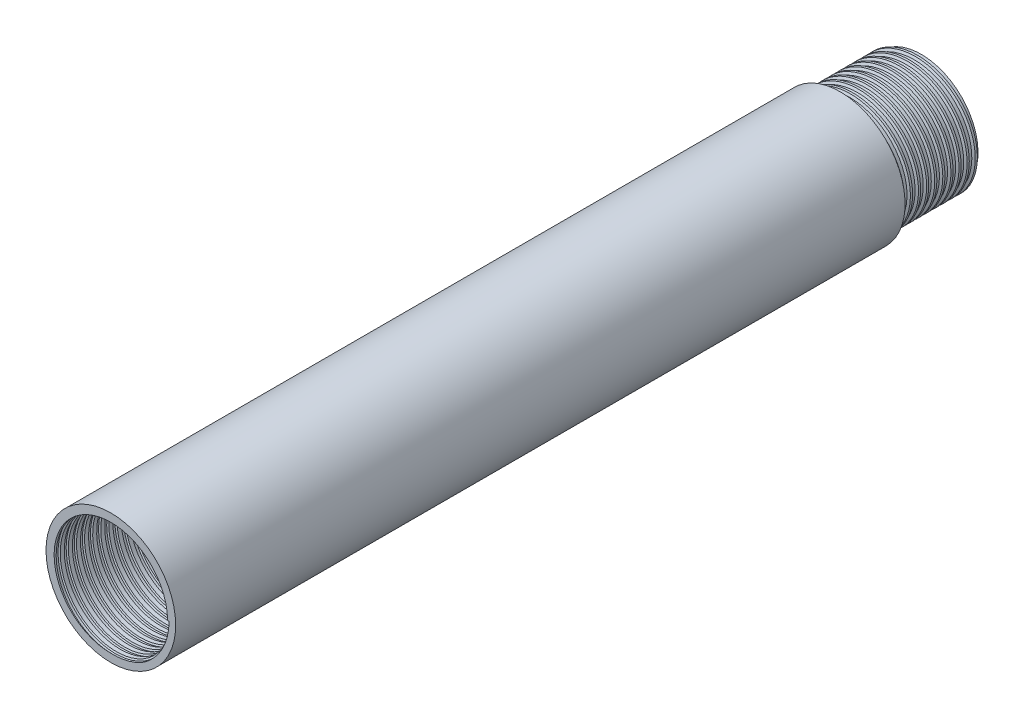
SolidWorks part; units mm, degrees
ref_plane "Front Plane" through (0, 0, 0) normal (0, 0, 1) x (1, 0, 0)
ref_plane "Top Plane" through (0, 0, 0) normal (0, 1, 0) x (1, 0, 0)
ref_plane "Right Plane" through (0, 0, 0) normal (1, 0, 0) x (0, 0, -1)
sketch "Sketch1" plane through (0, 0, 0) normal (0, 0, 1) x (1, 0, 0)
  circle A0 centre (0, 0) radius 9
  circle A1 centre (0, 0) radius 12
  dimension "D1" = 18
  dimension "D2" = 24
extrude "Boss-Extrude1" add sketch "Sketch1" along normal blind 150
sketch "Sketch2" plane through (0, 0, 0) normal (0, 0, -1) x (-1, 0, 0)
  circle A0 centre (0, 0) radius 12
  circle A1 centre (0, 0) radius 10.5
  dimension "D1" = 21
extrude "Cut-Extrude1" cut sketch "Sketch2" against normal blind 15
sketch "Sketch8" plane through (0, 0, 150) normal (0, 0, 1) x (1, 0, 0)
  circle A0 centre (0, 0) radius 9
  circle A1 centre (0, 0) radius 10.5
  dimension "D1" = 21
extrude "Cut-Extrude3" cut sketch "Sketch8" against normal blind 15
sketch "Sketch9" plane through (0, 0, 150) normal (0, 0, 1) x (1, 0, 0)
  circle A0 centre (0, 0) radius 10.25
curve "Helix/Spiral3" pitch 1.5 height 15 turns 10
sketch "Sketch10" plane through (0, 0, 0) normal (0, 1, 0) x (1, 0, 0)
  line L0 (10.2387, -148.4889) -> (10.7749, -148.4889) construction
  line L5 (10.2387, -147.9889) -> (10.2387, -148.9889)
  line L6 (10.2387, -148.9889) -> (10.7749, -148.7389)
  line L7 (10.7749, -148.7389) -> (10.7749, -148.2389)
  line L8 (10.2387, -147.9889) -> (10.7749, -148.2389)
  spline S1 degree 3 poles (10.25, -150) (10.25, -149.969) (9.7163, -149.9062) (7.4365, -149.8125) (4.0246, -149.7187) (0, -149.625) (-4.0246, -149.5312) (-7.4365, -149.4375) (-9.7163, -149.3437) (-10.5168, -149.25) (-9.7163, -149.1562) (-7.4365, -149.0625) (-2.8873, -148.9375) (2.8873, -148.8125) (7.4365, -148.6875) (9.7163, -148.5937) (10.5168, -148.5) (9.7163, -148.4062) (7.4365, -148.3125) (2.8873, -148.1875) (-2.8873, -148.0625) (-7.4365, -147.9375) (-9.7163, -147.8437) (-10.5168, -147.75) (-9.7163, -147.6562) (-7.4365, -147.5625) (-2.8873, -147.4375) (2.8873, -147.3125) (7.4365, -147.1875) (9.7163, -147.0938) (10.5168, -147) (9.7163, -146.9062) (7.4365, -146.8125) (2.8873, -146.6875) (-2.8873, -146.5625) (-7.4365, -146.4375) (-9.7163, -146.3438) (-10.5168, -146.25) (-9.7163, -146.1562) (-7.4365, -146.0625) (-2.8873, -145.9375) (2.8873, -145.8125) (7.4365, -145.6875) (9.7163, -145.5937) (10.5168, -145.5) (9.7163, -145.4062) (7.4365, -145.3125) (2.8873, -145.1875) (-2.8873, -145.0625) (-7.4365, -144.9375) (-9.7163, -144.8438) (-10.5168, -144.75) (-9.7163, -144.6562) (-7.4365, -144.5625) (-2.8873, -144.4375) (2.8873, -144.3125) (7.4365, -144.1875) (9.7163, -144.0937) (10.5168, -144) (9.7163, -143.9062) (7.4365, -143.8125) (2.8873, -143.6875) (-2.8873, -143.5625) (-7.4365, -143.4375) (-9.7163, -143.3437) (-10.5168, -143.25) (-9.7163, -143.1562) (-7.4365, -143.0625) (-2.8873, -142.9375) (2.8873, -142.8125) (7.4365, -142.6875) (9.7163, -142.5938) (10.5168, -142.5) (9.7163, -142.4062) (7.4365, -142.3125) (2.8873, -142.1875) (-2.8873, -142.0625) (-7.4365, -141.9375) (-9.7163, -141.8438) (-10.5168, -141.75) (-9.7163, -141.6562) (-7.4365, -141.5625) (-2.8873, -141.4375) (2.8873, -141.3125) (7.4365, -141.1875) (9.7163, -141.0938) (10.5168, -141) (9.7163, -140.9062) (7.4365, -140.8125) (2.8873, -140.6875) (-2.8873, -140.5625) (-7.4365, -140.4375) (-9.7163, -140.3437) (-10.5168, -140.25) (-9.7163, -140.1563) (-7.4365, -140.0625) (-2.8873, -139.9375) (2.8873, -139.8125) (7.4365, -139.6875) (9.7163, -139.5938) (10.5168, -139.5) (9.7163, -139.4062) (7.4365, -139.3125) (2.8873, -139.1875) (-2.8873, -139.0625) (-7.4365, -138.9375) (-9.7163, -138.8438) (-10.5168, -138.75) (-9.7163, -138.6562) (-7.4365, -138.5625) (-2.8873, -138.4375) (2.8873, -138.3125) (7.4365, -138.1875) (9.7163, -138.0937) (10.5168, -138) (9.7163, -137.9062) (7.4365, -137.8125) (2.8873, -137.6875) (-2.8873, -137.5625) (-7.4365, -137.4375) (-9.7163, -137.3437) (-10.5168, -137.25) (-9.7163, -137.1562) (-7.4365, -137.0625) (-2.8873, -136.9375) (2.8873, -136.8125) (7.4365, -136.6875) (9.7163, -136.5938) (10.5168, -136.5) (9.7163, -136.4063) (7.4365, -136.3125) (2.8873, -136.1875) (-2.8873, -136.0625) (-7.4365, -135.9375) (-9.7163, -135.8438) (-10.5168, -135.75) (-9.7163, -135.6563) (-7.4365, -135.5625) (-4.0246, -135.4688) (0, -135.375) (4.0246, -135.2813) (7.4365, -135.1875) (9.7163, -135.0938) (10.25, -135.031) (10.25, -135) knots 0 0 0 0 0.00625 0.0125 0.01875 0.025 0.03125 0.0375 0.04375 0.05 0.05625 0.0625 0.06875 0.08125 0.0875 0.09375 0.1 0.10625 0.1125 0.11875 0.13125 0.1375 0.14375 0.15 0.15625 0.1625 0.16875 0.18125 0.1875 0.19375 0.2 0.20625 0.2125 0.21875 0.23125 0.2375 0.24375 0.25 0.25625 0.2625 0.26875 0.28125 0.2875 0.29375 0.3 0.30625 0.3125 0.31875 0.33125 0.3375 0.34375 0.35 0.35625 0.3625 0.36875 0.38125 0.3875 0.39375 0.4 0.40625 0.4125 0.41875 0.43125 0.4375 0.44375 0.45 0.45625 0.4625 0.46875 0.48125 0.4875 0.49375 0.5 0.50625 0.5125 0.51875 0.53125 0.5375 0.54375 0.55 0.55625 0.5625 0.56875 0.58125 0.5875 0.59375 0.6 0.60625 0.6125 0.61875 0.63125 0.6375 0.64375 0.65 0.65625 0.6625 0.66875 0.68125 0.6875 0.69375 0.7 0.70625 0.7125 0.71875 0.73125 0.7375 0.74375 0.75 0.75625 0.7625 0.76875 0.78125 0.7875 0.79375 0.8 0.80625 0.8125 0.81875 0.83125 0.8375 0.84375 0.85 0.85625 0.8625 0.86875 0.88125 0.8875 0.89375 0.9 0.90625 0.9125 0.91875 0.93125 0.9375 0.94375 0.95 0.95625 0.9625 0.96875 0.975 0.98125 0.9875 0.99375 1 1 1 1 construction
  dimension "D1" = 0.5
  dimension "D2" = 0.25
  dimension "D3" = 65
sweep "Cut-Sweep1" cut profiles "Sketch10" path "Helix/Spiral3"
sketch "Sketch11" plane through (0, 0, 0) normal (0, 0, -1) x (-1, 0, 0)
  circle A0 centre (0, 0) radius 10.5
curve "Helix/Spiral4" pitch 1.5 height 15 turns 10
sketch "Sketch12" plane through (0, 0, 0) normal (0, 1, 0) x (1, 0, 0)
  line L0 (-10.5, -1.5) -> (-10.9289, -1.5) construction
  line L1 (-10.5, 0) -> (-10.5, -15) construction
  line L2 (-10.5, -1.9) -> (-10.5, -1.1)
  line L3 (-10.5, -1.1) -> (-10.9289, -1.3)
  line L4 (-10.9289, -1.3) -> (-10.9289, -1.7)
  line L5 (-10.5, -1.9) -> (-10.9289, -1.7)
  spline S0 degree 3 poles (-10.5, 0) (-10.5, -0.031) (-9.9533, -0.0938) (-7.6179, -0.1875) (-4.1228, -0.2813) (0, -0.375) (4.1228, -0.4688) (7.6179, -0.5625) (9.9533, -0.6563) (10.7734, -0.75) (9.9533, -0.8438) (7.6179, -0.9375) (2.9577, -1.0625) (-2.9577, -1.1875) (-7.6179, -1.3125) (-9.9533, -1.4063) (-10.7734, -1.5) (-9.9533, -1.5938) (-7.6179, -1.6875) (-2.9577, -1.8125) (2.9577, -1.9375) (7.6179, -2.0625) (9.9533, -2.1562) (10.7734, -2.25) (9.9533, -2.3438) (7.6179, -2.4375) (2.9577, -2.5625) (-2.9577, -2.6875) (-7.6179, -2.8125) (-9.9533, -2.9063) (-10.7734, -3) (-9.9533, -3.0938) (-7.6179, -3.1875) (-2.9577, -3.3125) (2.9577, -3.4375) (7.6179, -3.5625) (9.9533, -3.6563) (10.7734, -3.75) (9.9533, -3.8438) (7.6179, -3.9375) (2.9577, -4.0625) (-2.9577, -4.1875) (-7.6179, -4.3125) (-9.9533, -4.4063) (-10.7734, -4.5) (-9.9533, -4.5938) (-7.6179, -4.6875) (-2.9577, -4.8125) (2.9577, -4.9375) (7.6179, -5.0625) (9.9533, -5.1563) (10.7734, -5.25) (9.9533, -5.3438) (7.6179, -5.4375) (2.9577, -5.5625) (-2.9577, -5.6875) (-7.6179, -5.8125) (-9.9533, -5.9063) (-10.7734, -6) (-9.9533, -6.0938) (-7.6179, -6.1875) (-2.9577, -6.3125) (2.9577, -6.4375) (7.6179, -6.5625) (9.9533, -6.6563) (10.7734, -6.75) (9.9533, -6.8438) (7.6179, -6.9375) (2.9577, -7.0625) (-2.9577, -7.1875) (-7.6179, -7.3125) (-9.9533, -7.4063) (-10.7734, -7.5) (-9.9533, -7.5938) (-7.6179, -7.6875) (-2.9577, -7.8125) (2.9577, -7.9375) (7.6179, -8.0625) (9.9533, -8.1563) (10.7734, -8.25) (9.9533, -8.3438) (7.6179, -8.4375) (2.9577, -8.5625) (-2.9577, -8.6875) (-7.6179, -8.8125) (-9.9533, -8.9063) (-10.7734, -9) (-9.9533, -9.0938) (-7.6179, -9.1875) (-2.9577, -9.3125) (2.9577, -9.4375) (7.6179, -9.5625) (9.9533, -9.6563) (10.7734, -9.75) (9.9533, -9.8438) (7.6179, -9.9375) (2.9577, -10.0625) (-2.9577, -10.1875) (-7.6179, -10.3125) (-9.9533, -10.4063) (-10.7734, -10.5) (-9.9533, -10.5938) (-7.6179, -10.6875) (-2.9577, -10.8125) (2.9577, -10.9375) (7.6179, -11.0625) (9.9533, -11.1563) (10.7734, -11.25) (9.9533, -11.3438) (7.6179, -11.4375) (2.9577, -11.5625) (-2.9577, -11.6875) (-7.6179, -11.8125) (-9.9533, -11.9063) (-10.7734, -12) (-9.9533, -12.0938) (-7.6179, -12.1875) (-2.9577, -12.3125) (2.9577, -12.4375) (7.6179, -12.5625) (9.9533, -12.6563) (10.7734, -12.75) (9.9533, -12.8438) (7.6179, -12.9375) (2.9577, -13.0625) (-2.9577, -13.1875) (-7.6179, -13.3125) (-9.9533, -13.4062) (-10.7734, -13.5) (-9.9533, -13.5937) (-7.6179, -13.6875) (-2.9577, -13.8125) (2.9577, -13.9375) (7.6179, -14.0625) (9.9533, -14.1562) (10.7734, -14.25) (9.9533, -14.3437) (7.6179, -14.4375) (4.1228, -14.5312) (0, -14.625) (-4.1228, -14.7187) (-7.6179, -14.8125) (-9.9533, -14.9062) (-10.5, -14.969) (-10.5, -15) knots 0 0 0 0 0.00625 0.0125 0.01875 0.025 0.03125 0.0375 0.04375 0.05 0.05625 0.0625 0.06875 0.08125 0.0875 0.09375 0.1 0.10625 0.1125 0.11875 0.13125 0.1375 0.14375 0.15 0.15625 0.1625 0.16875 0.18125 0.1875 0.19375 0.2 0.20625 0.2125 0.21875 0.23125 0.2375 0.24375 0.25 0.25625 0.2625 0.26875 0.28125 0.2875 0.29375 0.3 0.30625 0.3125 0.31875 0.33125 0.3375 0.34375 0.35 0.35625 0.3625 0.36875 0.38125 0.3875 0.39375 0.4 0.40625 0.4125 0.41875 0.43125 0.4375 0.44375 0.45 0.45625 0.4625 0.46875 0.48125 0.4875 0.49375 0.5 0.50625 0.5125 0.51875 0.53125 0.5375 0.54375 0.55 0.55625 0.5625 0.56875 0.58125 0.5875 0.59375 0.6 0.60625 0.6125 0.61875 0.63125 0.6375 0.64375 0.65 0.65625 0.6625 0.66875 0.68125 0.6875 0.69375 0.7 0.70625 0.7125 0.71875 0.73125 0.7375 0.74375 0.75 0.75625 0.7625 0.76875 0.78125 0.7875 0.79375 0.8 0.80625 0.8125 0.81875 0.83125 0.8375 0.84375 0.85 0.85625 0.8625 0.86875 0.88125 0.8875 0.89375 0.9 0.90625 0.9125 0.91875 0.93125 0.9375 0.94375 0.95 0.95625 0.9625 0.96875 0.975 0.98125 0.9875 0.99375 1 1 1 1 construction
  dimension "D1" = 0.4
  dimension "D2" = 0.2
  dimension "D3" = 65
sweep "Sweep3" add profiles "Sketch12" path "Helix/Spiral4"
sketch "Sketch13" plane through (0, 0, 0) normal (0, 0, -1) x (-1, 0, 0)
  circle A0 centre (0, 0) radius 12.7633
extrude "Cut-Extrude4" cut sketch "Sketch13" along normal blind 5
sketch "Sketch14" plane through (0, 0, 135) normal (0, 0, 1) x (1, 0, 0)
  circle A0 centre (0, 0) radius 9
  circle A1 centre (0, 0) radius 6.3627
extrude "Boss-Extrude2" add sketch "Sketch14" against normal blind 3
